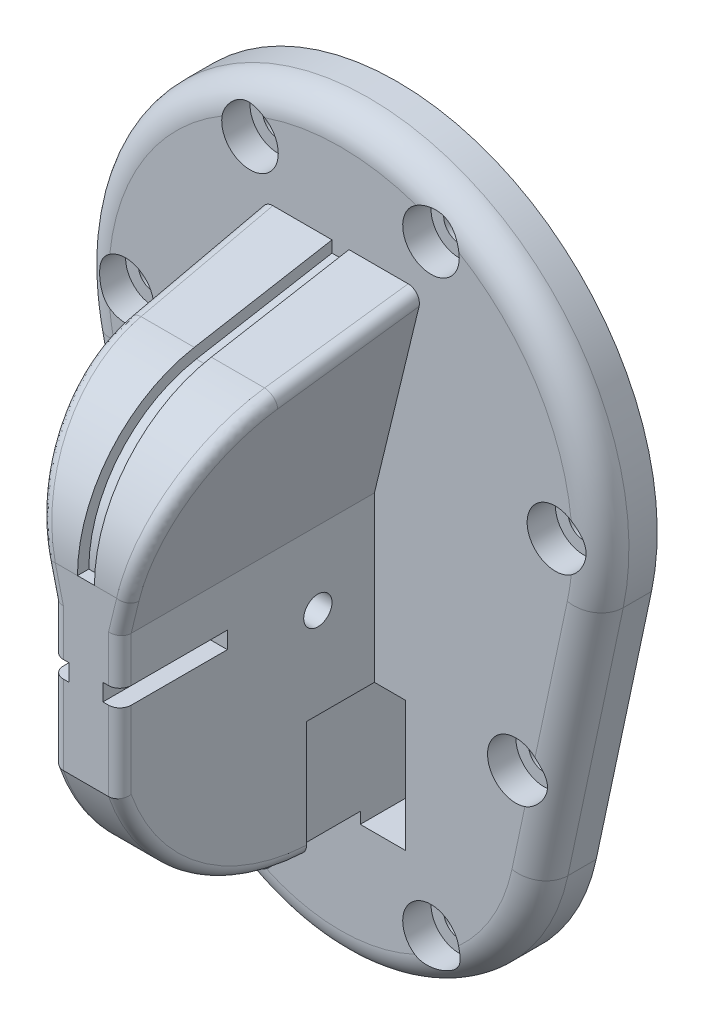
SolidWorks part; units mm, degrees
other "Objet de détail2"
material "Alliage 1060"
ref_plane "Plan de face" through (0, 0, 0) normal (0, 0, 1) x (1, 0, 0)
ref_plane "Plan de dessus" through (0, 0, 0) normal (0, 1, 0) x (1, 0, 0)
ref_plane "Plan de droite" through (0, 0, 0) normal (1, 0, 0) x (0, 0, -1)
sketch "Base" plane through (0, 0, 0) normal (0, 0, 1) x (1, 0, 0)
  line L0 (0, 46) -> (0, -84) construction
  line L1 (-44.9907, -9.5833) -> (-35.2101, -55.5)
  line L2 (44.9907, -9.5833) -> (35.2101, -55.5)
  line L3 (-38, 0) -> (38, 0) construction
  line L4 (-16, 34.4674) -> (16, 34.4674) construction
  line L5 (-16, -72) -> (16, -72) construction
  line L6 (-38, 0) -> (-31, -39) construction
  line L7 (-31, -39) -> (31, -39) construction
  line L8 (3.5, -61) -> (-3.5, -61) construction
  line L9 (-3.5, -61) -> (-11.5, -61)
  line L10 (-3.5, -61) -> (-3.5, -38)
  line L11 (-3.5, -38) -> (-11.5, -38)
  line L12 (-11.5, -61) -> (-11.5, -38)
  line L13 (3.5, -38) -> (11.5, -38)
  line L14 (3.5, -38) -> (3.5, -61)
  line L15 (3.5, -61) -> (11.5, -61)
  line L16 (11.5, -38) -> (11.5, -61)
  circle A0 centre (0, 0) radius 46 construction
  circle A1 centre (0, -48) radius 36 construction
  arc A2 (-44.9907, -9.5833) -> (44.9907, -9.5833) centre (0, 0) cw
  arc A3 (-35.2101, -55.5) -> (35.2101, -55.5) centre (0, -48) ccw
  circle A4 centre (-38, 0) radius 2.75
  circle A5 centre (38, 0) radius 2.75
  circle A6 centre (0, 0) radius 38 construction
  circle A7 centre (-16, 34.4674) radius 2.75
  circle A8 centre (16, 34.4674) radius 2.75
  circle A9 centre (0, -48) radius 28.8444 construction
  circle A10 centre (-16, -72) radius 2.75
  circle A11 centre (16, -72) radius 2.75
  circle A12 centre (-31, -39) radius 2.75
  circle A13 centre (31, -39) radius 2.75
  point P29 (0, 34.4674)
  point P32 (0, -39)
  point P41 (0, -61)
  dimension "D2" = 92
  dimension "D3" = 72
  dimension "D5" = 5.5
  dimension "D1" = 130
  dimension "D4" = 76
  dimension "D6" = 32
  dimension "D7" = 31
  dimension "D8" = 38
  dimension "D9" = 39
  dimension "D10" = 33
  dimension "D11" = 23
  dimension "D12" = 62
  dimension "D13" = 23
  dimension "D14" = 8
  dimension "D15" = 7
other "AlignerGroupe1"
sketch "Esquisse1" plane through (0, 0, 0) normal (0, 0, 1) x (1, 0, 0)
  line L0 (-44.9907, -9.5833) -> (-35.2101, -55.5)
  line L1 (35.2101, -55.5) -> (44.9907, -9.5833)
  arc A0 (-44.9907, -9.5833) -> (44.9907, -9.5833) centre (0, 0) cw
  arc A1 (-35.2101, -55.5) -> (35.2101, -55.5) centre (0, -48) ccw
extrude "Boss.-Extru.2" add sketch "Esquisse1" along normal blind 10
fillet "Congé1" radius 5 4 edges at (-40.1004, -32.5417, 10) (0, 46, 10) (40.1004, -32.5417, 10) (0, -84, 10)
hole_wizard "Perçage1" positions "Esquisse2" profile "Esquisse3" legacy end condition through all
sketch "Esquisse2" plane through (0, 0, 10) normal (0, 0, 1) x (1, 0, 0)
  point P0 (38, 0)
  point P5 (16, 34.4674)
  point P8 (-16, 34.4674)
  point P11 (-38, 0)
  point P14 (-31, -39)
  point P17 (-16, -72)
  point P20 (16, -72)
  point P23 (31, -39)
sketch "Esquisse3" plane through (38, 0, 10) normal (1, 0, 0) x (0, -1, 0)
  line L0 (0, 0) -> (0, 11.6524)
  line L1 (0, 11.6524) -> (2.75, 10)
  line L2 (2.75, 10) -> (2.75, 5)
  line L3 (2.75, 5) -> (5, 5)
  line L4 (5, 0) -> (0, 0)
  line L5 (0, -11.3109) -> (0, 121.1557) construction
  line L6 (0, 11.6524) -> (-2.75, 10) construction
  line L7 (5, 5) -> (5, 0)
  dimension "Diamètre" = 5.5
  dimension "Profondeur" = 10
  dimension "Diamètre chambrage" = 10
  dimension "Profondeur chambrage" = 5
  dimension "Angle" = 118
sketch "Esquisse4" plane through (0, 0, 0) normal (0, 0, 1) x (1, 0, 0)
  line L1 (-11.5, -38) -> (-3.5, -38)
  line L2 (-11.5, -38) -> (-11.5, -61)
  line L3 (-11.5, -61) -> (-3.5, -61)
  line L4 (-3.5, -38) -> (-3.5, -61)
  line L5 (3.5, -38) -> (11.5, -38)
  line L6 (3.5, -38) -> (3.5, -61)
  line L7 (3.5, -61) -> (11.5, -61)
  line L8 (11.5, -38) -> (11.5, -61)
extrude "Enlèv. mat.-Extru.1" cut sketch "Esquisse4" along normal through all
sketch "Esquisse5" plane through (0, 0, 10) normal (0, 0, 1) x (1, 0, 0)
  line L0 (0, 46) -> (0, -84) construction
  line L1 (-6, -59) -> (6, -59)
  line L2 (-6, -59) -> (-6, -9)
  line L4 (6, -59) -> (6, -9)
  line L6 (6, -9) -> (14.5, 26)
  line L7 (14.5, 26) -> (-14.5, 26)
  line L8 (-14.5, 26) -> (-6, -9)
  line L9 (-6, -9) -> (6, -9) construction
  line L10 (3.5, -61) -> (-3.5, -61) construction
  point P4 (0, 26)
  point P5 (0, -59)
  dimension "D1" = 12
  dimension "D2" = 29
  dimension "D3" = 50
  dimension "D4" = 20
  dimension "D5" = 2
extrude "Boss.-Extru.5" add sketch "Esquisse5" along normal blind 45
sketch "Esquisse6" plane through (0, 0, 0) normal (1, 0, 0) x (0, 0, -1)
  line L0 (-10, -38) -> (-10, -9) construction
  line L1 (-20, -59) -> (-20, -22) construction
  line L2 (-55, -9) -> (-55, 26) construction
  line L3 (-10, -54.4583) -> (-10, -70.9131) construction
  line L4 (-55, -59) -> (-55, -9) construction
  line L5 (-20, -59) -> (-55, -59)
  line L6 (-55, -59) -> (-55, -34)
  line L7 (-10, 26) -> (-34.3412, 21.708)
  line L10 (-10, 26) -> (-55, 26)
  line L11 (-55, 26) -> (-55, -2.9122)
  circle A0 centre (-20, -22) radius 37 construction
  arc A1 (-20, -59) -> (-55, -34) centre (-20, -22) cw
  arc A2 (-34.3412, 21.708) -> (-55, -2.9122) centre (-30, -2.9122) ccw
  circle A3 centre (-20, -22) radius 2.5
  dimension "D6" = 5
  dimension "D7" = 25
  dimension "D1" = 62
  dimension "D2" = 68
  dimension "D3" = 10
  dimension "D4" = 10
  dimension "D5" = 10
extrude "Enlèv. mat.-Extru.2" cut sketch "Esquisse6" against normal mid plane 45
sketch "Esquisse7" plane through (0, 0, 10) normal (0, 0, -1) x (-1, 0, 0)
  line L0 (3.5, -38) -> (3.5, -59) construction
  line L1 (3.5, -59) -> (6, -59) construction
  line L2 (6, -59) -> (6, -38) construction
  line L3 (6, -38) -> (3.5, -38) construction
  line L4 (-3.5, -59) -> (-3.5, -38) construction
  line L5 (-3.5, -38) -> (-6, -38) construction
  line L6 (-6, -38) -> (-6, -59) construction
  line L7 (-6, -59) -> (-3.5, -59) construction
  line L8 (3.5, -38) -> (3.5, -59)
  line L9 (3.5, -59) -> (6, -59)
  line L10 (6, -59) -> (6, -38)
  line L11 (6, -38) -> (3.5, -38)
  line L12 (-3.5, -59) -> (-3.5, -38)
  line L13 (-3.5, -38) -> (-6, -38)
  line L14 (-6, -38) -> (-6, -59)
  line L15 (-6, -59) -> (-3.5, -59)
extrude "Enlèv. mat.-Extru.3" cut sketch "Esquisse7" against normal blind 12
fillet "Congé2" radius 2 10 edges at (-13.9788, 23.854, 22.1706) (11.3811, 13.1575, 49.1511) (-11.3811, 13.1575, 49.1511) (-6, -21.5, 55) (-6, -51.5157, 42.312) (6, -51.5157, 42.312) (6, -21.5, 55) (13.9788, 23.854, 22.1706) (-6.7392, -5.9561, 55) (6.7392, -5.9561, 55)
sketch "Esquisse8" plane through (0, 0, 0) normal (1, 0, 0) x (0, 0, -1)
  line L0 (-10, 26) -> (-34.3412, 21.708) construction
  line L1 (-10, 26) -> (-34.3412, 21.708)
  line L2 (-10, 23.9691) -> (-33.9939, 19.7384)
  line L3 (-9.6527, 24.0304) -> (-33.9939, 19.7384) construction
  line L4 (-10, 23.9691) -> (-10, 26)
  line L5 (-53, -2.9122) -> (-55, -2.9122)
  arc A0 (-34.3412, 21.708) -> (-55, -2.9122) centre (-30, -2.9122) ccw construction
  arc A1 (-34.3412, 21.708) -> (-55, -2.9122) centre (-30, -2.9122) ccw
  arc A2 (-33.9939, 19.7384) -> (-53, -2.9122) centre (-30, -2.9122) ccw
  arc A3 (-33.9939, 19.7384) -> (-53, -2.9122) centre (-30, -2.9122) ccw construction
  dimension "D1" = 2
extrude "Enlèv. mat.-Extru.4" cut sketch "Esquisse8" against normal mid plane 3
sketch "Esquisse9" plane through (-6, 0, 0) normal (-1, 0, 0) x (0, 0, 1)
  line L0 (55, -8.7606) -> (55, -34) construction
  line L1 (36, -20) -> (55, -20)
  line L2 (36, -20) -> (36, -17)
  line L3 (36, -17) -> (55, -17)
  line L4 (55, -20) -> (55, -17)
  line L5 (22, -38) -> (22, -22) construction
  line L6 (22, -22) -> (20, -22) construction
  line L7 (22, -22) -> (36, -22) construction
  line L8 (36, -22) -> (36, -20) construction
  line L10 (36, -18.5) -> (20, -18.5) construction
  line L11 (20, -18.5) -> (20, -22) construction
  line L12 (20, -22) -> (20, -38) construction
  line L13 (20, -59) -> (20, -22) construction
  line L14 (22, -38) -> (0, -38) construction
  line L15 (22, -38) -> (10, -38) construction
  dimension "D1" = 3
extrude "Enlèv. mat.-Extru.5" cut sketch "Esquisse9" against normal blind 3
mirror "Symétrie1" about plane through (0, 0, 0) normal (1, 0, 0) of "Enlèv. mat.-Extru.5"
sketch "Esquisse11" plane through (0, 0, 0) normal (0, 0, -1) x (-1, 0, 0)
  line L4 (36.1863, -36.5171) -> (42.0565, -8.9583)
  line L5 (-34.7242, -43.3809) -> (-32.2759, -54.875)
  line L8 (-42.0565, -8.9583) -> (-32.2759, -54.875)
  line L9 (32.2759, -54.875) -> (42.0565, -8.9583)
  line L10 (-42.0565, -8.9583) -> (-36.1863, -36.5171)
  line L11 (32.2759, -54.875) -> (34.7242, -43.3809)
  line L22 (14.5, -35) -> (0.5, -35)
  line L23 (0.5, -35) -> (0.5, -64)
  line L24 (0.5, -64) -> (14.5, -64)
  line L25 (14.5, -64) -> (14.5, -35)
  line L26 (14.5, -35) -> (0.5, -35)
  line L27 (0.5, -35) -> (0.5, -64)
  line L28 (0.5, -64) -> (14.5, -64)
  line L29 (14.5, -64) -> (14.5, -35)
  line L37 (-0.5, -35) -> (-14.5, -35)
  line L38 (-0.5, -64) -> (-0.5, -35)
  line L39 (-14.5, -64) -> (-0.5, -64)
  line L40 (-14.5, -35) -> (-14.5, -64)
  line L41 (-0.5, -35) -> (-14.5, -35)
  line L42 (-0.5, -64) -> (-0.5, -35)
  line L43 (-14.5, -64) -> (-0.5, -64)
  line L44 (-14.5, -35) -> (-14.5, -64)
  arc A8 (42.0565, -8.9583) -> (-42.0565, -8.9583) centre (0, 0) ccw
  arc A9 (-32.2759, -54.875) -> (32.2759, -54.875) centre (0, -48) ccw
  arc A10 (42.0565, -8.9583) -> (42.8939, -3.0186) centre (0, 0) ccw
  arc A11 (-32.2759, -54.875) -> (-21.6827, -72.8769) centre (0, -48) ccw
  circle A12 centre (31, -39) radius 5.75
  arc A13 (36.1863, -36.5171) -> (34.7242, -43.3809) centre (31, -39) ccw
  arc A14 (21.6827, -72.8769) -> (32.2759, -54.875) centre (0, -48) ccw
  circle A15 centre (16, -72) radius 5.75
  arc A16 (21.6827, -72.8769) -> (14.6237, -77.5829) centre (16, -72) ccw
  circle A22 centre (-16, -72) radius 5.75
  arc A23 (-14.6237, -77.5829) -> (-21.6827, -72.8769) centre (-16, -72) ccw
  circle A25 centre (-31, -39) radius 5.75
  arc A26 (-34.7242, -43.3809) -> (-36.1863, -36.5171) centre (-31, -39) ccw
  circle A28 centre (-38, 0) radius 5.75
  arc A29 (-42.8939, -3.0186) -> (-42.8939, 3.0186) centre (-38, 0) ccw
  circle A31 centre (-16, 34.4674) radius 5.75
  arc A32 (-20.7986, 37.6353) -> (-15.3226, 40.1773) centre (-16, 34.4674) ccw
  circle A34 centre (16, 34.4674) radius 5.75
  arc A35 (15.3226, 40.1773) -> (20.7986, 37.6353) centre (16, 34.4674) ccw
  arc A36 (-14.6237, -77.5829) -> (14.6237, -77.5829) centre (0, -48) ccw
  circle A37 centre (38, 0) radius 5.75
  arc A38 (42.8939, 3.0186) -> (42.8939, -3.0186) centre (38, 0) ccw
  arc A39 (-42.8939, -3.0186) -> (-42.0565, -8.9583) centre (0, 0) ccw
  arc A40 (-20.7986, 37.6353) -> (-42.8939, 3.0186) centre (0, 0) ccw
  arc A41 (15.3226, 40.1773) -> (-15.3226, 40.1773) centre (0, 0) ccw
  arc A42 (42.8939, 3.0186) -> (20.7986, 37.6353) centre (0, 0) ccw
  dimension "D1" = 3
  dimension "D2" = 3
  dimension "D3" = 3
  dimension "D4" = 3
  dimension "D5" = 3
  dimension "D6" = 3
  dimension "D7" = 3
  dimension "D8" = 3
  dimension "D9" = 3
  dimension "D10" = 3
  dimension "D11" = 3
extrude "Enlèv. mat.-Extru.6" cut sketch "Esquisse11" against normal blind 4
